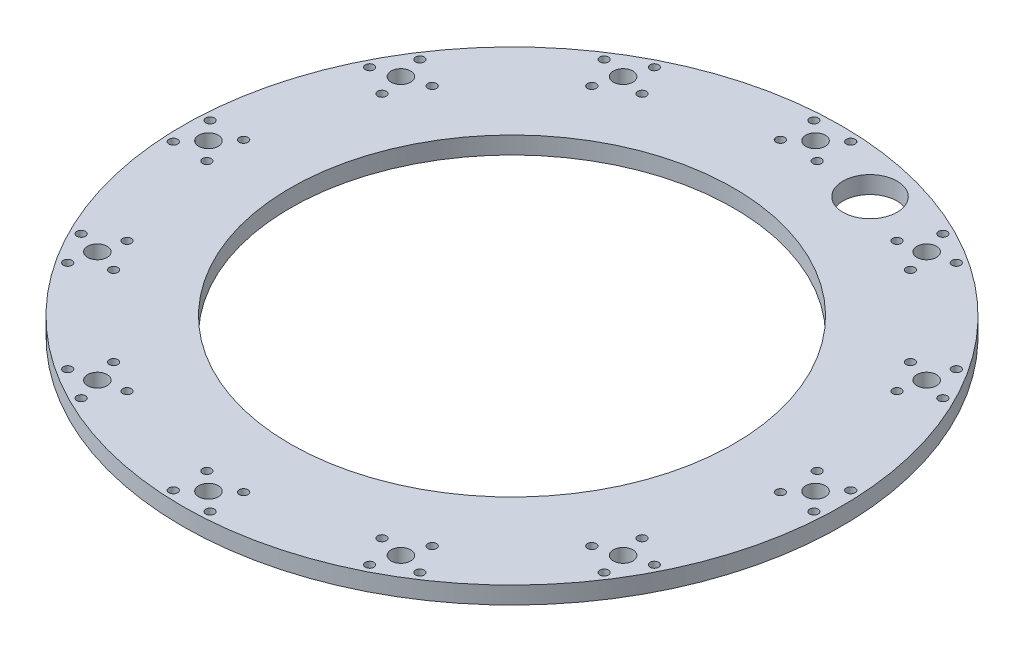
SolidWorks part; units mm, degrees
material "Balsa"
ref_plane "Ebene vorne" through (0, 0, 0) normal (0, 0, 1) x (1, 0, 0)
ref_plane "Ebene oben" through (0, 0, 0) normal (0, 1, 0) x (1, 0, 0)
ref_plane "Ebene rechts" through (0, 0, 0) normal (1, 0, 0) x (0, 0, -1)
sketch "Sketch1" plane through (0, 0, 0) normal (0, 1, 0) x (1, 0, 0)
  circle A0 centre (0, 0) radius 51.2
  circle A1 centre (0, 0) radius 76.1
  dimension "D1" = 152.2
  dimension "D2" = 102.4
extrude "Boss-Extrude1" add sketch "Sketch1" along normal blind 4
sketch "Sketch2" plane through (0, 4, 0) normal (0, 1, 0) x (1, 0, 0)
  line L0 (0, 78.5044) -> (0, 60.1888) construction
  line L1 (7.9546, 70.0914) -> (-11.9341, 70.0914) construction
  circle A0 centre (0, 70.0914) radius 2.25
  circle A1 centre (4.2466, 73.9682) radius 1
  circle A2 centre (4.2466, 66.2147) radius 1
  circle A3 centre (-4.2466, 66.2147) radius 1
  circle A4 centre (-4.2466, 73.9682) radius 1
  point P15 (0, 0)
  point P16 (0, 0)
  point P17 (0, 0)
  point P18 (0, 0)
  point P19 (0, 0)
  point P20 (0, 0)
  point P21 (4.2466, 66.0318)
  dimension "D1" = 4.5
  dimension "D3" = 2
  dimension "D2" = 11.5
extrude "Cut-Extrude1" cut sketch "Sketch2" against normal through all
ref_axis "Axis1" through (0, -0.2, 0) along (0, 1, 0)
pattern_circular "CirPattern1" count 12 over 360 about axis through (0, -0.2, 0) along (0, 1, 0) of "Cut-Extrude1"
sketch "Sketch3" plane through (0, 4, 0) normal (0, 1, 0) x (1, 0, 0)
  line L0 (17.4703, 65.2) -> (0, 0) construction
  line L1 (0, 0) -> (0, 80.521) construction
  circle A0 centre (17.4703, 65.2) radius 6.25
  dimension "D1" = 12.5
  dimension "D3" = 15
  dimension "D2" = 67.5
extrude "Cut-Extrude2" cut sketch "Sketch3" against normal blind 10
